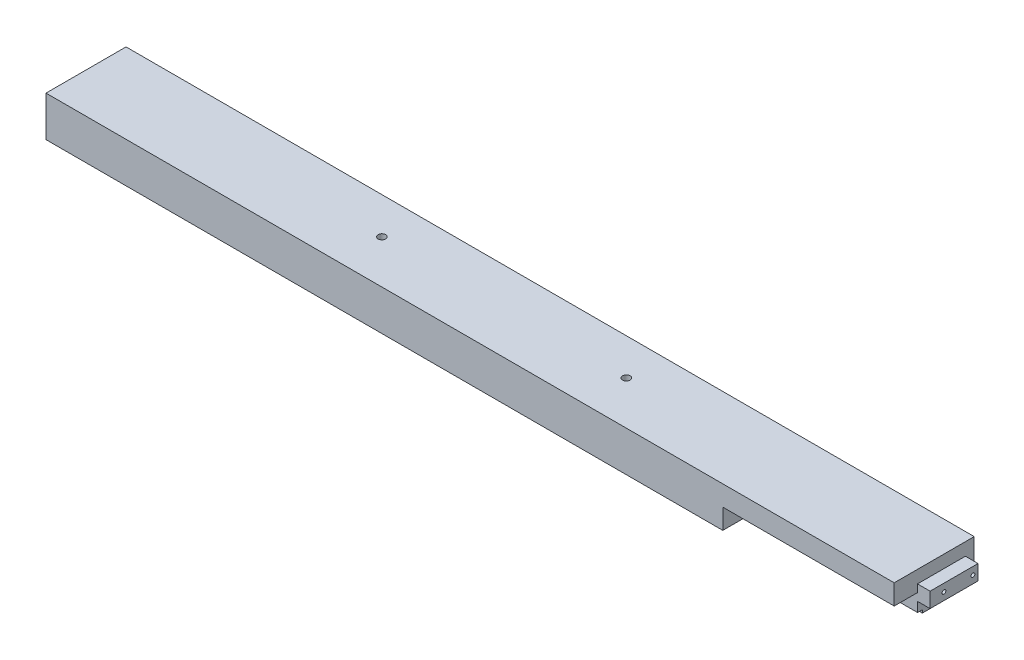
SolidWorks part; units mm, degrees
ref_plane "Front Plane" through (0, 0, 0) normal (0, 0, 1) x (1, 0, 0)
ref_plane "Top Plane" through (0, 0, 0) normal (0, 1, 0) x (1, 0, 0)
ref_plane "Right Plane" through (0, 0, 0) normal (1, 0, 0) x (0, 0, -1)
sketch "Sketch1" plane through (0, 0, 0) normal (0, 1, 0) x (1, 0, 0)
  line L1 (1068.3875, 100.8063) -> (-1068.3875, 100.8062)
  line L2 (1068.3875, 100.8063) -> (1068.3875, -100.8062)
  line L3 (1068.3875, -100.8062) -> (-1068.3875, -100.8063)
  line L4 (-1068.3875, 100.8062) -> (-1068.3875, -100.8063)
  line L5 (1068.3875, 100.8063) -> (-1068.3875, -100.8063) construction
  line L6 (1068.3875, -100.8062) -> (-1068.3875, 100.8062) construction
  point P0 (0, 0)
  dimension "D1" = 201.6125
  dimension "D2" = 2136.775
extrude "Boss-Extrude1" add sketch "Sketch1" along normal blind 101.6
sketch "Sketch2" plane through (0, 101.6, 0) normal (0, 1, 0) x (1, 0, 0)
  line L0 (-1068.3875, 100.8062) -> (-1068.3875, -100.8063) construction
  line L1 (1068.3875, 100.8063) -> (-1068.3875, 100.8062) construction
  circle A0 centre (-331.7875, 8.7313) radius 9.525
  circle A1 centre (284.1625, 8.7313) radius 9.525
  dimension "D1" = 19.05
  dimension "D2" = 615.95
  dimension "D3" = 736.6
  dimension "D4" = 92.075
extrude "Cut-Extrude1" cut sketch "Sketch2" against normal through all
sketch "Sketch3" plane through (1068.3875, 0, 0) normal (1, 0, 0) x (0, 0, -1)
  line L0 (-100.8062, 0) -> (100.8063, 0) construction
  line L1 (-42.0687, 69.85) -> (78.5813, 69.85)
  line L2 (-42.0687, 69.85) -> (-42.0687, 31.75)
  line L3 (-42.0687, 31.75) -> (78.5813, 31.75)
  line L4 (78.5813, 69.85) -> (78.5813, 31.75)
  line L5 (-42.0687, 69.85) -> (78.5813, 31.75) construction
  line L6 (-42.0687, 31.75) -> (78.5813, 69.85) construction
  line L7 (18.2563, 50.8) -> (78.5813, 50.8) construction
  line L8 (100.8063, 101.6) -> (100.8063, 0) construction
  line L9 (-100.8062, 50.8) -> (-42.0687, 50.8)
  line L10 (-100.8062, 101.6) -> (-100.8062, 0) construction
  line L11 (-42.0687, 50.8) -> (-42.0687, 7.3123)
  line L12 (-42.0687, 7.3123) -> (-29.932, 7.3123)
  line L13 (-29.932, 7.3123) -> (-29.932, 0)
  line L14 (-100.8062, 50.8) -> (-100.8062, 0)
  line L15 (-100.8062, 0) -> (-29.932, 0)
  circle A0 centre (65.8813, 50.8) radius 4.7625
  circle A1 centre (-7.1437, 50.8) radius 4.7625
  point P0 (18.2563, 50.8)
  point P15 (-42.0687, 50.8)
  line M6 (-100.8062, 0) -> (100.8063, 0)
  line M9 (-100.8062, 101.6) -> (-100.8062, 0)
  dimension "D4" = 9.525
  dimension "D1" = 38.1
  dimension "D2" = 31.75
  dimension "D3" = 120.65
  dimension "D5" = 34.925
  dimension "D6" = 22.225
  dimension "D7" = 73.025
extrude "Boss-Extrude2" add sketch "Sketch3" along normal blind 31.75 contours L4 L1 L2 L3 A1 A0 region at (1068.3875, 50.8, -17.9007)
extrude "Cut-Extrude2" cut sketch "Sketch3<3>" against normal blind 431.8 contours L13 L12 L11 L2 L9 M9 M6 region at (1068.3875, 24.772, 70.414)
sketch "Sketch3<3>" plane through (1068.3875, 0, 0) normal (1, 0, 0) x (0, 0, -1) same geometry as "Sketch3"
sketch "Sketch5" plane through (0, 0, 0) normal (0, -1, 0) x (1, 0, 0)
  line L1 (1068.3875, -100.8063) -> (-1068.3875, -100.8062) construction
  circle A0 centre (1009.3067, 7.1437) radius 11.1125
  circle A1 centre (1009.3067, -65.8813) radius 11.1125
  dimension "D1" = 22.225
  dimension "D2" = 73.025
  dimension "D3" = 34.925
extrude "Cut-Extrude3" cut sketch "Sketch5" against normal blind 69.85
